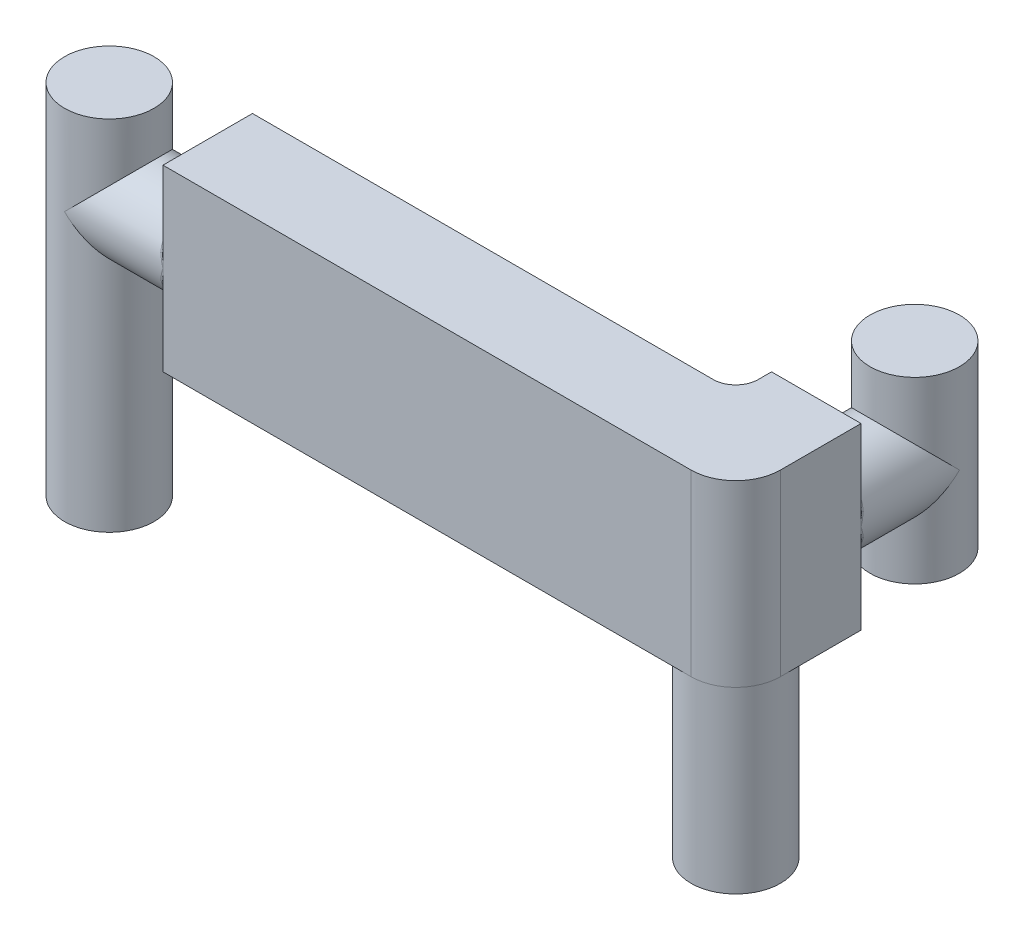
SolidWorks part; units mm, degrees
ref_plane "Front Plane" through (0, 0, 0) normal (0, 0, 1) x (1, 0, 0)
ref_plane "Top Plane" through (0, 0, 0) normal (0, 1, 0) x (1, 0, 0)
ref_plane "Right Plane" through (0, 0, 0) normal (1, 0, 0) x (0, 0, -1)
sketch "Sketch2" plane through (0, 0, 0) normal (0, 1, 0) x (1, 0, 0)
  circle A0 centre (0, 0) radius 2.5
  dimension "D1" = 5
extrude "Boss-Extrude2" add sketch "Sketch2" along normal blind 10
sketch "Sketch3" plane through (0, 0, 0) normal (1, 0, 0) x (0, 0, -1)
  line L0 (0, 0) -> (0, 10) construction
  line L1 (2.5, 10) -> (-2.5, 10) construction
  line L2 (-2.5, 5) -> (2.5, 5) construction
  line L3 (-2.5, 10) -> (-2.5, 0) construction
  line L4 (2.5, 0) -> (2.5, 10) construction
  circle A0 centre (0, 5) radius 2.5
  dimension "D1" = 5
extrude "Boss-Extrude3" add sketch "Sketch3" along normal blind 5.5
sketch "Sketch4" plane through (0, 0, 0) normal (0, 1, 0) x (1, 0, 0)
  line L0 (5.5, -2.5) -> (5.5, 2.5) construction
  line L1 (5.5, 2.5) -> (32.5, 2.5)
  line L2 (5.5, 2.5) -> (5.5, -2.5)
  line L3 (5.5, -2.5) -> (37.5, -2.5)
  line L6 (32.5, 4.5) -> (37.5, 4.5)
  line L7 (32.5, 4.5) -> (32.5, 2.5)
  line L9 (37.5, 4.5) -> (37.5, -2.5)
  dimension "D1" = 5
  dimension "D3" = 2.5
  dimension "D4" = 0
  dimension "D5" = 5
  dimension "D2" = 7
  dimension "D6" = 27
extrude "Boss-Extrude4" add sketch "Sketch4" along normal blind 10
sketch "Sketch8" plane through (0, 0, 0) normal (0, -1, 0) x (1, 0, 0)
  circle A1 centre (0, 0) radius 2.5
  circle A2 centre (0, 0) radius 2.5
  dimension "D1" = 0
extrude "Boss-Extrude6" add sketch "Sketch8" along normal blind 10
sketch "Sketch9" plane through (0, 0, 0) normal (0, -1, 0) x (1, 0, 0)
  line L0 (35, -4.5) -> (35, 0) construction
  line L1 (37.5, -4.5) -> (32.5, -4.5) construction
  line L2 (35, 0) -> (0, 0) construction
  circle A0 centre (35, 0) radius 2.5
  dimension "D1" = 5
extrude "Boss-Extrude7" add sketch "Sketch9" along normal blind 10
sketch "Sketch10" plane through (0, 0, -4.5) normal (0, 0, -1) x (-1, 0, 0)
  line L2 (-35, 10) -> (-35, 0) construction
  line L3 (-37.5, 10) -> (-32.5, 10) construction
  line L4 (-37.5, 0) -> (-32.5, 0) construction
  line L5 (-37.5, 5) -> (-32.5, 5) construction
  line L6 (-37.5, 10) -> (-37.5, 0) construction
  line L7 (-32.5, 10) -> (-32.5, 0) construction
  circle A0 centre (-35, 5) radius 2.5
  dimension "D1" = 5
extrude "Boss-Extrude8" add sketch "Sketch10" along normal blind 5.5
sketch "Sketch11" plane through (0, 0, 0) normal (0, 1, 0) x (1, 0, 0)
  line L0 (37.5, 10) -> (32.5, 10) construction
  circle A0 centre (35, 10) radius 2.5
  dimension "D1" = 5
extrude "Boss-Extrude9" add sketch "Sketch11" along normal blind 10
fillet "Fillet3" radius 0.25 4 edges at (5.5, 2.5, 0) (35, 2.5, -4.5) (35, 7.5, -4.5) (5.5, 7.5, 0)
fillet "Fillet4" radius 2.5 1 edges at (37.5, 5, 2.5)
fillet "Fillet5" radius 1.25 1 edges at (32.5, 5, -2.5)
equation "\"D3@Sketch4\"=\"D1@Sketch4\"/2"
